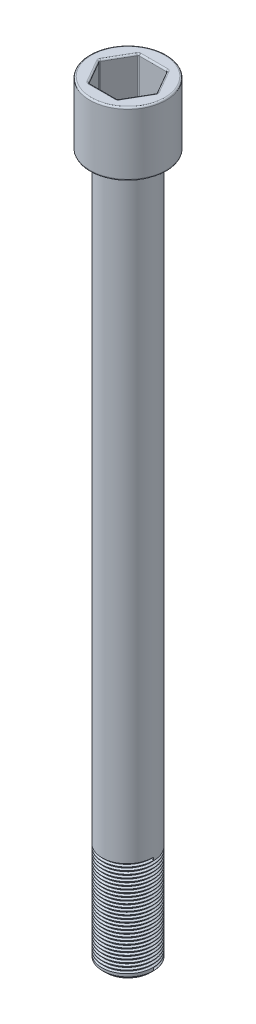
SolidWorks part; units mm, degrees
material "AISI 4140 Steel, quenched & tempered"
ref_plane "Front Plane" through (0, 0, 0) normal (1, 0, 0) x (0, 1, 0)
ref_plane "Top Plane" through (0, 0, 0) normal (0, 0, 1) x (0, 1, 0)
ref_plane "Right Plane" through (0, 0, 0) normal (0, 1, 0) x (-1, 0, 0)
sketch "Sketch1" plane through (0, 0, 0) normal (1, 0, 0) x (0, 1, 0)
  line L0 (-122.9929, 0) -> (42.9358, 0) construction
  line L1 (0, 23.268) -> (0, -20.4189) construction
  line L2 (10, 0) -> (10, 6)
  line L3 (10, 6) -> (0, 6)
  line L4 (0, 6) -> (0, 4)
  line L5 (0, 4) -> (-110, 4)
  line L6 (-110, 4) -> (-110, 0)
  line L7 (-110, 0) -> (10, 0)
  dimension "D1" = 10
  dimension "D2" = 12
  dimension "D3" = 8
  dimension "D4" = 110
revolve "Revolve1" add sketch "Sketch1" angle 360 about L0
sketch "Sketch2" plane through (0, 10, 0) normal (0, 1, 0) x (-1, 0, 0)
  line L1 (2.25, -3.8971) -> (4.5, 0)
  line L2 (4.5, 0) -> (2.25, 3.8971)
  line L3 (2.25, 3.8971) -> (-2.25, 3.8971)
  line L4 (-2.25, 3.8971) -> (-4.5, 0)
  line L5 (-4.5, 0) -> (-2.25, -3.8971)
  line L6 (-2.25, -3.8971) -> (2.25, -3.8971)
  circle A0 centre (0, 0) radius 3.8971 construction
  dimension "D1" = 4.5
extrude "Cut-Extrude1" cut sketch "Sketch2" against normal blind 8
ref_axis "Axis1" through (0, 16, 0) along (0, -1, 0)
thread "Thread2" pitch 0.5 method cut profile "Thread Profile2" start angle 0, offset 0.5, length 15, pitch 0.5, diameter 8
ref_plane "Plane2" through (4, -109.5, 0) normal (0, 0, 1) x (1, 0, 0)
sketch "Thread Profile2" plane through (4, -109.5, 0) normal (0, 0, 1) x (1, 0, 0)
  line L0 (0, 0) -> (0, 0.5) construction
  line L11 (0, 0) -> (0, 0.4375)
  line L12 (0, 0.4375) -> (-0.2706, 0.2812)
  line L13 (-0.2706, 0.2812) -> (-0.2706, 0.1562)
  line L15 (-0.2706, 0.1562) -> (0, 0)
  line L17 (-0.2706, 0.2187) -> (0, 0.2187) construction
  point P2 (0, 0)
  dimension "Pitch" = 0.5
  dimension "Profile_Angle" = 60
  dimension "Profile_Land" = 0.125
  dimension "Profile_Height" = 0.2706
chamfer "Chamfer1" distance 0.5 angle 45 1 edges at (0, -110, -4)
fillet "Fillet1" radius 0.25 20 edges at (0, 0, -6) (0, 10, -6) (0, 10, -3.8971) (-3.375, 10, -1.9486) (-3.375, 10, 1.9486) (0, 10, 3.8971) (3.375, 10, 1.9486) (3.375, 10, -1.9486) (0, 2, -3.8971) (-3.375, 2, -1.9486) (-3.375, 2, 1.9486) (0, 2, 3.8971) (3.375, 2, 1.9486) (3.375, 2, -1.9486) (-2.25, 6, -3.8971) (-2.25, 6, 3.8971) (2.25, 6, 3.8971) (4.5, 6, 0) (2.25, 6, -3.8971) (-4.5, 6, 0)
